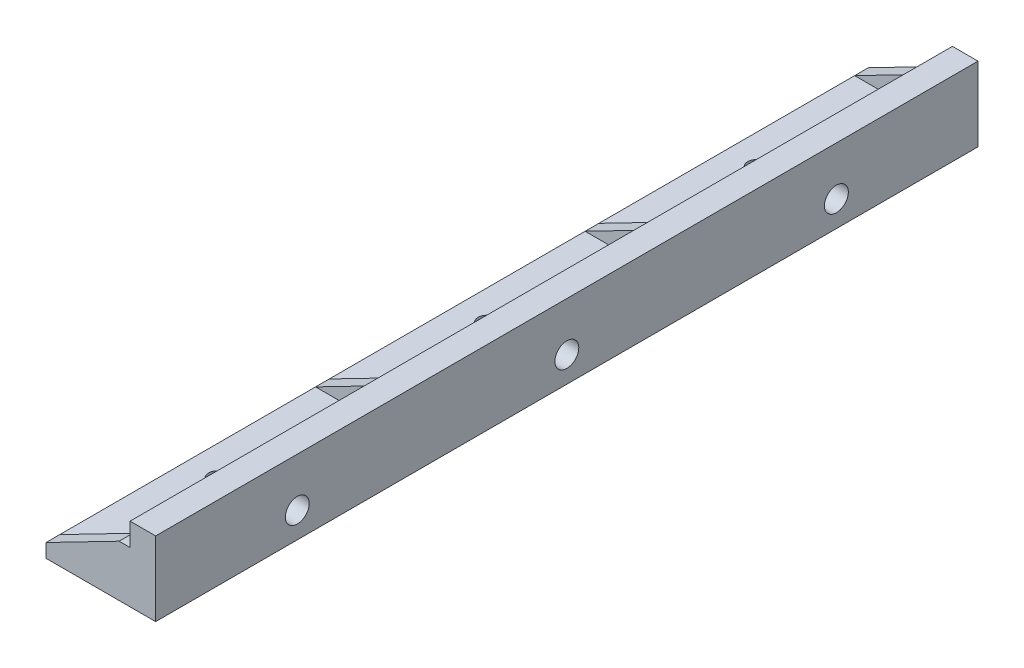
SolidWorks part; units mm, degrees
ref_plane "Front Plane" through (0, 0, 0) normal (0, 0, 1) x (1, 0, 0)
ref_plane "Top Plane" through (0, 0, 0) normal (0, 1, 0) x (1, 0, 0)
ref_plane "Right Plane" through (0, 0, 0) normal (1, 0, 0) x (0, 0, -1)
sketch "Sketch1" plane through (0, 0, 0) normal (0, 0, 1) x (1, 0, 0)
  line L0 (0, 0) -> (0, 11.25)
  line L1 (0, 11.25) -> (-8, 11.25)
  line L2 (-8, 11.25) -> (-8, 6)
  line L3 (-11, 3) -> (-24, 3)
  line L4 (-24, 3) -> (-24, 0)
  line L6 (-24, 0) -> (0, 0)
  arc A0 (-8, 6) -> (-11, 3) centre (-11, 6) cw
  dimension "D1" = 3
  dimension "D2" = 11.25
  dimension "D3" = 24
  dimension "D4" = 8
  dimension "D5" = 3
extrude "Boss-Extrude1" add sketch "Sketch1" along normal blind 180
ref_plane "Plane2" through (0, 0, 0) normal (0, 0, -1) x (-1, 0, 0)
ref_plane "Plane4" through (0, 0, 90) normal (0, 0, -1) x (-1, 0, 0)
ref_plane "Plane5" through (0, 0, 60.5) normal (0, 0, -1) x (-1, 0, 0)
sketch "Sketch4" plane through (0, 0, 60.5) normal (0, 0, -1) x (-1, 0, 0)
  line L0 (8, 11.25) -> (24, 3)
sketch "Sketch5" plane through (0, 0, 0) normal (0, 0, -1) x (-1, 0, 0)
  line L0 (8, 11.25) -> (24, 3)
rib "Rib3" sketch "Sketch4" sketch "Sketch4" thickness 3 extrusion direction parallel to sketch draft on no parameters "D1"=3
rib "Rib4" sketch "Sketch5" sketch "Sketch5" thickness 3 extrusion direction parallel to sketch draft on no parameters "D1"=3
mirror "Mirror1" about plane through (0, 0, 90) normal (0, 0, -1) of "Rib3", "Rib4"
sketch "Sketch6" plane through (0, 0, 0) normal (1, 0, 0) x (0, 0, -1)
  line L0 (-180, 5.625) -> (0, 5.625) construction
  line L1 (-180, 0) -> (-180, 11.25) construction
  line L2 (0, 0) -> (0, 11.25) construction
  circle A0 centre (-149, 5.625) radius 2.3495
  circle A1 centre (-31, 5.625) radius 2.3495
  circle A2 centre (-90, 5.625) radius 2.3495
  point P6 (-149, 5.625)
  point P7 (-31, 5.625)
  point P8 (-90, 5.625)
  dimension "D3" = 4.699
  dimension "D1" = 31
  dimension "D2" = 31
sketch "Sketch9" plane through (0, 0, 0) normal (0, -1, 0) x (1, 0, 0)
  line L0 (-17.5, 180) -> (-17.5, 0) construction
  line L1 (-24, 180) -> (0, 180) construction
  line L2 (-24, 0) -> (0, 0) construction
  line L3 (-24, 180) -> (-24, 0) construction
  point P6 (-17.5, 149)
  point P7 (-17.5, 31)
  point P10 (-17.5, 90)
  dimension "D1" = 31
  dimension "D2" = 31
  dimension "D3" = 6.5
hole_wizard "#6 Clearance Hole1" positions "Sketch10" profile "Sketch11" hole size "#6" standard "ANSI Inch" end condition through all
sketch "Sketch10" plane through (0, 0, 0) normal (0, -1, 0) x (-1, 0, 0)
  point P0 (17.5, -31)
  point P3 (17.5, -149)
  point P6 (17.5, -90)
sketch "Sketch11" plane through (-17.5, 0, 31) normal (1, 0, 0) x (0, 0, -1)
  line L0 (0, 0) -> (0, 11.25)
  line L1 (0, 11.25) -> (1.8986, 11.25)
  line L2 (1.8986, 11.25) -> (1.8986, 0)
  line L5 (1.8986, 0) -> (0, 0)
  line L11 (0, -6.35) -> (0, 107.95) construction
  dimension "Thru Hole Dia." = 3.7973
  dimension "Thru Hole Depth" = 11.25
extrude "Cut-Extrude1" cut sketch "Sketch6" against normal offset from surface (7 mm away) 1 up to face at (-8, 8.625, 149)
sketch "Sketch12" plane through (0, 0, 0) normal (1, 0, 0) x (0, 0, -1)
  circle A0 centre (-149, 5.625) radius 2.6162
  circle A1 centre (-31, 5.625) radius 2.6162
  circle A2 centre (-90, 5.625) radius 2.6162
  dimension "D1" = 5.2324
extrude "Cut-Extrude2" cut sketch "Sketch12" against normal blind 6.35
sketch "Sketch13" plane through (0, 11.25, 0) normal (0, 1, 0) x (1, 0, 0)
  line L1 (0, 0) -> (-5.6, 0)
  line L2 (0, 0) -> (0, -180)
  line L3 (0, -180) -> (-5.6, -180)
  line L4 (-5.6, 0) -> (-5.6, -180)
  dimension "D1" = 5.6
extrude "Boss-Extrude2" add sketch "Sketch13" along normal blind 5
